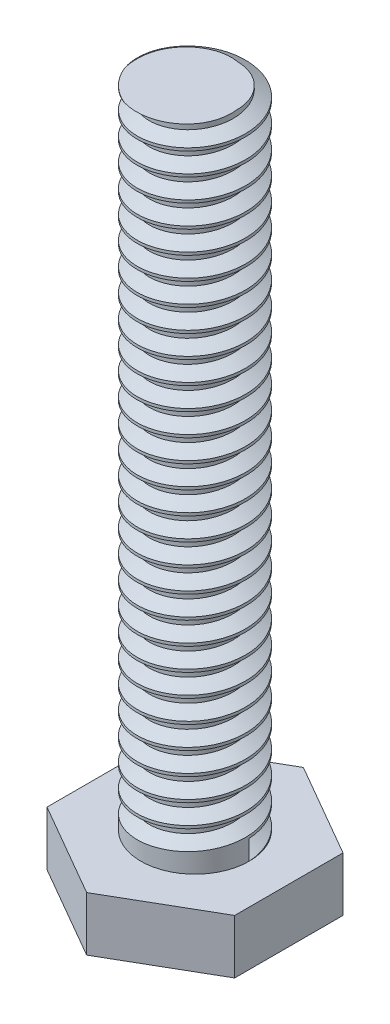
SolidWorks part; units mm, degrees
ref_plane "Front" through (0, 0, 0) normal (0, 0, 1) x (1, 0, 0)
ref_plane "Top" through (0, 0, 0) normal (0, 1, 0) x (1, 0, 0)
ref_plane "Right" through (0, 0, 0) normal (1, 0, 0) x (0, 0, -1)
sketch "Sketch1" plane through (0, 0, 0) normal (0, 1, 0) x (1, 0, 0)
  circle A0 centre (0, 0) radius 5.08
  dimension "D1" = 10.16
extrude "Boss-Extrude1" add sketch "Sketch1" along normal blind 60.452
sketch "Sketch2" plane through (0, 0, 0) normal (0, -1, 0) x (1, 0, 0)
  line L1 (0, 10.16) -> (-8.7988, 5.08)
  line L2 (-8.7988, 5.08) -> (-8.7988, -5.08)
  line L3 (-8.7988, -5.08) -> (0, -10.16)
  line L4 (0, -10.16) -> (8.7988, -5.08)
  line L5 (8.7988, -5.08) -> (8.7988, 5.08)
  line L6 (8.7988, 5.08) -> (0, 10.16)
  circle A0 centre (0, 0) radius 8.7988 construction
  dimension "D1" = 10.16
extrude "Boss-Extrude2" add sketch "Sketch2" along normal blind 5.08
thread "Thread1" pitch 2.1167 profile "Thread Profile1" start angle 0, offset 0, length 121.92, pitch 2.1167, diameter 10.16
ref_plane "Plane1" through (5.08, 0, 0) normal (0, 0, 1) x (1, 0, 0)
sketch "Thread Profile1" plane through (5.08, 0, 0) normal (0, 0, 1) x (1, 0, 0)
  line L0 (0, 0) -> (0, 2.1167) construction
  line L11 (0, 0) -> (0, 1.8521)
  line L12 (0, 1.8521) -> (-1.1457, 1.1906)
  line L13 (-1.1457, 1.1906) -> (-1.1457, 0.6615)
  line L15 (-1.1457, 0.6615) -> (0, 0)
  line L17 (-1.1457, 0.926) -> (0, 0.926) construction
  point P2 (0, 0)
  dimension "Pitch" = 2.1167
  dimension "Profile_Angle" = 60
  dimension "Profile_Land" = 0.5292
  dimension "Profile_Height" = 1.1457
